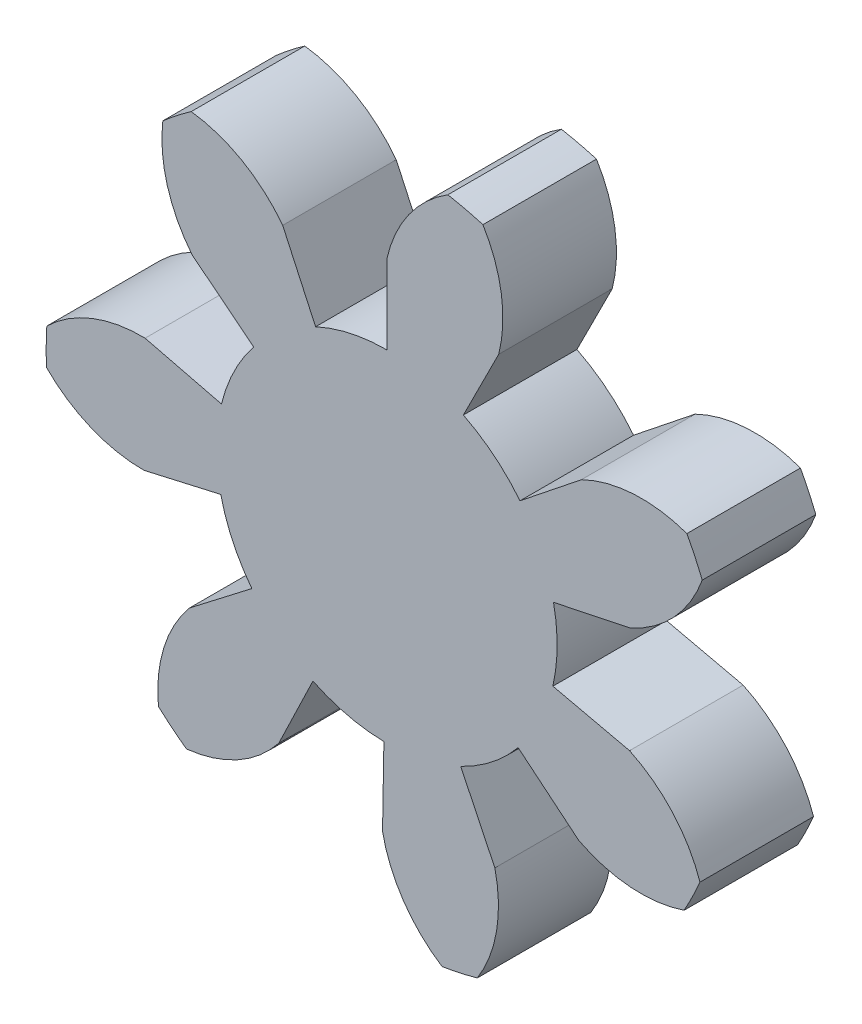
SolidWorks part; units mm, degrees
ref_plane "Plan de face" through (0, 0, 0) normal (0, 0, 1) x (1, 0, 0)
ref_plane "Plan de dessus" through (0, 0, 0) normal (0, 1, 0) x (1, 0, 0)
ref_plane "Plan de droite" through (0, 0, 0) normal (1, 0, 0) x (0, 0, -1)
sketch "Esquisse1" plane through (0, 0, 0) normal (0, 0, 1) x (1, 0, 0)
  circle A0 centre (0, 0) radius 7
  circle A1 centre (0, 0) radius 9
  circle A2 centre (0, 0) radius 4.5
  circle A3 centre (0, 0) radius 5
  circle A4 centre (0, 0) radius 6.5778
  dimension "Pitch Circle" = 14
  dimension "Addendum Circle" = 18
  dimension "Root Circle" = 9
  dimension "Clearence Circle" = 10
  dimension "Base Circle" = 13.1557
sketch "Involute" plane through (0, 0, 0) normal (0, 0, 1) x (1, 0, 0)
  line L0 (0, 0) -> (0, 6.5778)
  line L1 (0, 0) -> (3.2889, 5.6966) construction
  line L2 (0, 0) -> (5.6966, 3.2889) construction
  line L3 (0, 0) -> (6.5778, 0) construction
  line L4 (6.5778, 0) -> (6.5778, 10.3325) construction
  line L5 (5.6966, 3.2889) -> (2.2524, 9.2544) construction
  line L6 (3.2889, 5.6966) -> (0.3062, 7.4187) construction
  line L7 (0, 0) -> (3.0372, 6.3068) construction
  line L8 (5.4728, 4.3644) -> (0, 0)
  line L9 (1.6164, 6.8108) -> (0, 0) construction
  circle A0 centre (0, 0) radius 6.5778 construction
  circle A1 centre (0, 0) radius 7 construction
  arc A2 (3.0372, 6.3068) -> (0.1206, 6.999) centre (0, 0) ccw
  spline S0 degree 3 poles (0, 6.5778) (0.5786, 9.2716) (4.3581, 10.336) (6.5778, 10.3325) knots 0 0 0 0 1 1 1 1
  spline S1 degree 3 poles (2.9557, 5.8764) (3.6492, 8.5429) (0.751, 11.192) (-1.2336, 12.1863) knots 0 0 0 0 1 1 1 1
  dimension "Involute Control" = 90
  dimension "Base Circle Quarter Circumference" = 10.3325
  dimension "D1" = 6.8883
  dimension "D2" = 3.4442
  dimension "Circular Pitch" = 51.429
  dimension "Involute Array" = 4
sketch "Esquisse4" plane through (0, 0, 0) normal (0, 0, 1) x (1, 0, 0)
  line L0 (0, 0) -> (0, 6.5778) construction
  line L1 (0, 6.5778) -> (0, 4.5)
  line L2 (2.9557, 5.8764) -> (2.022, 4.0201)
  arc A0 (1.6117, 8.8545) -> (2.5389, 8.6345) centre (0, 0) cw
  circle A1 centre (0, 0) radius 9 construction
  arc A2 (0, 4.5) -> (2.022, 4.0201) centre (0, 0) cw
  circle A3 centre (0, 0) radius 4.5 construction
  arc A4 (0, 6.5778) -> (1.6117, 8.8545) centre (3.5132, 5.7996) cw
  arc A5 (2.5389, 8.6345) -> (2.9557, 5.8764) centre (-0.5325, 6.7598) cw
  spline S0 degree 3 poles (0, 6.5778) (0.5786, 9.2716) (4.3581, 10.336) (6.5778, 10.3325) knots 0 0 0 0 1 1 1 1 construction
  spline S1 degree 3 poles (2.9557, 5.8764) (3.6492, 8.5429) (0.751, 11.192) (-1.2336, 12.1863) knots 0 0 0 0 1 1 1 1 construction
extrude "Boss.-Extru.1" add sketch "Esquisse4" along normal blind 3
ref_axis "Axe1" through (0, 0, 0) along (0, 0, 1)
pattern_circular "Répétition circulaire2" count 7 over 360 about axis through (0, 0, 0) along (0, 0, 1) of bodies 101
sketch "Esquisse5" plane through (0, 0, 0) normal (0, 0, 1) x (1, 0, 0)
  circle A0 centre (0, 0) radius 4.5 construction
  circle A1 centre (0, 0) radius 4.5
extrude "Boss.-Extru.2" add sketch "Esquisse5" along normal up to surface (3 mm away) up to face at (-6.6458, 0.0572, 3)
equation "\"Module\"= 2"
equation "\"Nb de dents\"= 7"
equation "\"Pressure Angle\"= 20"
equation "\"Pitch Circle@Esquisse1\"= \"Module\" * \"Nb de dents\""
equation "\"Addendum Circle@Esquisse1\"= \"Pitch Circle@Esquisse1\" + ( \"Module\" * 2 )"
equation "\"Clearence Circle@Esquisse1\"= \"Pitch Circle@Esquisse1\" - ( \"Module\" * 2 )"
equation "\"Root Circle@Esquisse1\"= \"Pitch Circle@Esquisse1\" - ( ( \"Module\" * 1.25 ) * 2 )"
equation "\"Base Circle@Esquisse1\"= \"Pitch Circle@Esquisse1\" * cos ( \"Pressure Angle\" )"
equation "\"Base Circle Quarter Circumference@Involute\" = \"Base Circle@Esquisse1\" * pI / 4"
equation "\"D1@Involute\"=\"Base Circle Quarter Circumference@Involute\"/3*2"
equation "\"D2@Involute\"=\"Base Circle Quarter Circumference@Involute\"/3"
equation "\"Circular Pitch@Involute\"=360/\"Nb de dents\""
equation "\"D1@Répétition circulaire2\"= \"Nb de dents\""
